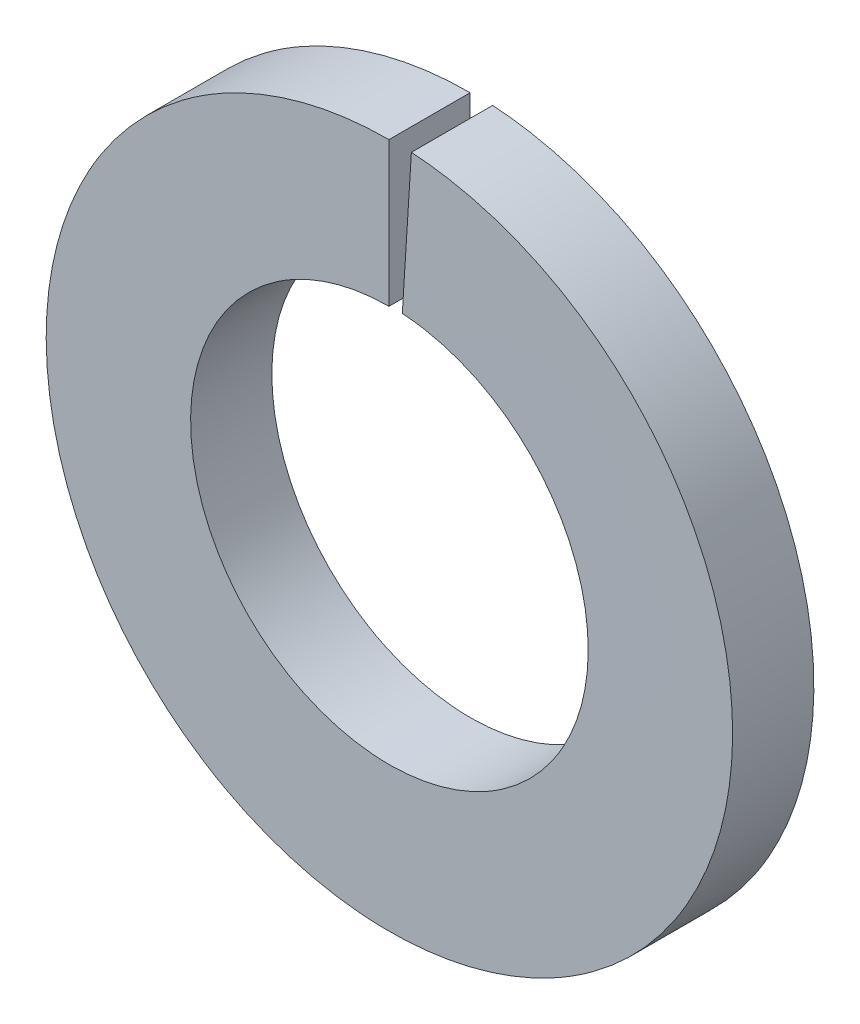
SolidWorks part; units mm, degrees
material "Alloy Steel"
ref_plane "Front Plane" through (0, 0, 0) normal (0, 0, 1) x (1, 0, 0)
ref_plane "Top Plane" through (0, 0, 0) normal (0, 1, 0) x (1, 0, 0)
ref_plane "Right Plane" through (0, 0, 0) normal (1, 0, 0) x (0, 0, -1)
sketch "Sketch1" plane through (0, 0, 0) normal (0, 0, 1) x (1, 0, 0)
  line L0 (0, 3.8) -> (0, 2.2) construction
  line L2 (0, -0.85) -> (0, 0.85) construction
  circle A0 centre (0, 0) radius 3.8 construction
  circle A1 centre (0, 0) radius 2.2 construction
  point P6 (2.2, 0)
  point P7 (-3.8, 0)
  point P8 (-2.2, 0)
  point P9 (0, 0)
  point P10 (3.8, 0)
  point P14 (0, 0)
  point P15 (0, 0.85)
  point P16 (0, -0.85)
  dimension "ID" = 4.4
  dimension "OD" = 7.6
  dimension "Overall Height" = 1.7
sketch "Sketch2" plane through (0, 0, 0) normal (1, 0, 0) x (0, 0, -1)
  line L1 (0, 3.8) -> (-0.9, 3.8) construction
  line L2 (0, 3.8) -> (0, 2.2) construction
  line L3 (0, 2.2) -> (-0.9, 2.2) construction
  line L4 (-0.9, 3.8) -> (-0.9, 2.2) construction
  point P5 (-0.9, 3.8)
  point P8 (0, 3.8)
  point P9 (0, 2.2)
  point P10 (-0.9, 2.2)
  dimension "THK" = 0.9
sketch "Sketch3" plane through (0, 0, 0) normal (0, 0, 1) x (1, 0, 0)
  circle A0 centre (0, 0) radius 3.8 construction
  circle A1 centre (0, 0) radius 3.8
curve "Helix/Spiral1" pitch 0.0101 height 0.01 radius 3.8 left hand yes centre (0, 0, 0) axis (0, 0, -1) start towards (0, 1, 0) parameters "Height"=0.01
sketch "Sketch4" plane through (0, 0, 0) normal (1, 0, 0) x (0, 0, -1)
  line L0 (-0.9, 3.8) -> (-0.9, 2.2) construction
  line L1 (0, 3.8) -> (0, 2.2) construction
  line L2 (0, 2.2) -> (-0.9, 2.2) construction
  line L3 (0, 3.8) -> (-0.9, 3.8) construction
  line L4 (-0.9, 3.8) -> (-0.9, 2.2)
  line L5 (0, 3.8) -> (0, 2.2)
  line L6 (0, 2.2) -> (-0.9, 2.2)
  line L7 (0, 3.8) -> (-0.9, 3.8)
sweep "Sweep1" add profiles "Sketch4" path "Helix/Spiral1"
ref_axis "Center Axis 1" through (0, 0, -6.9213) along (0, 0, 1)
ref_plane "Contact Plane 1" through (0, 0, 0.9) normal (0, 0, 1) x (1, 0, 0)
ref_plane "Contact Plane 2" through (0, 0, -0.01) normal (0, 0, 1) x (1, 0, 0)
